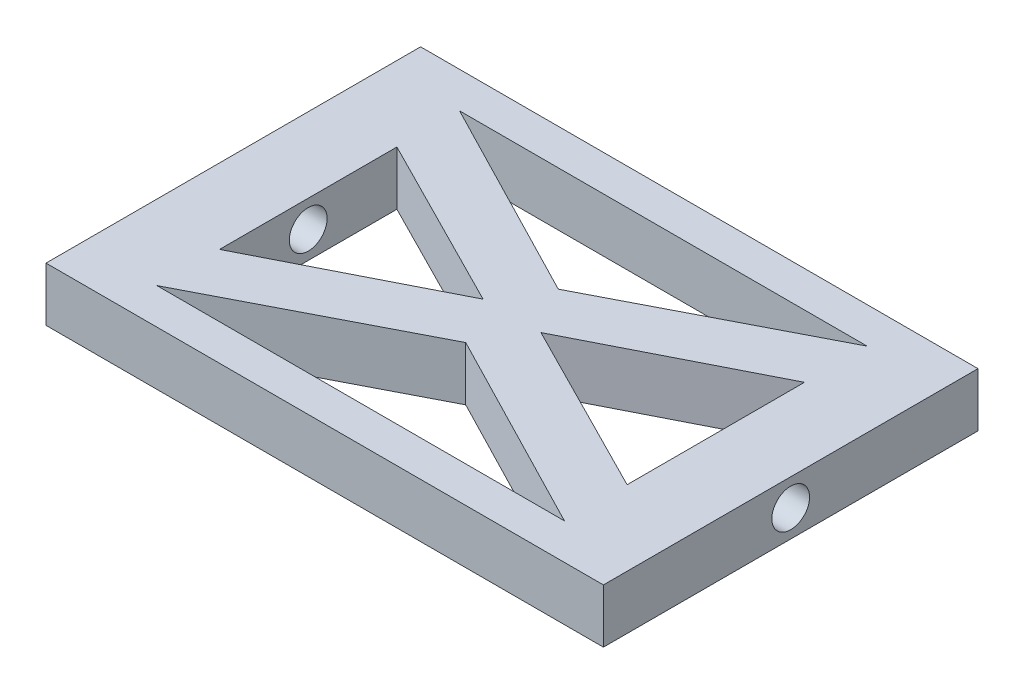
SolidWorks part; units mm, degrees
material "PLA"
ref_plane "Front" through (0, 0, 0) normal (0, 0, 1) x (1, 0, 0)
ref_plane "Top" through (0, 0, 0) normal (0, 1, 0) x (1, 0, 0)
ref_plane "Right" through (0, 0, 0) normal (1, 0, 0) x (0, 0, -1)
sketch "Sketch1" plane through (0, 0, 0) normal (0, 1, 0) x (1, 0, 0)
  line L1 (23.622, -15.875) -> (-23.622, -15.875)
  line L2 (23.622, -15.875) -> (23.622, 15.875)
  line L3 (23.622, 15.875) -> (-23.622, 15.875)
  line L4 (-23.622, -15.875) -> (-23.622, 15.875)
  line L5 (23.622, -15.875) -> (-23.622, 15.875) construction
  line L6 (23.622, 15.875) -> (-23.622, -15.875) construction
  point P0 (0, 0)
  dimension "D1" = 31.75
  dimension "D2" = 47.244
extrude "Boss-Extrude1" add sketch "Sketch1" along normal blind 4.572
sketch "Sketch2" plane through (0, 4.572, 0) normal (0, 1, 0) x (1, 0, 0)
  line L0 (-17.272, 3.175) -> (-17.272, 13.335)
  line L1 (-17.272, 13.335) -> (18.264, 13.335)
  line L2 (18.264, 13.335) -> (-17.272, 3.175)
  line L3 (23.622, 15.875) -> (-23.622, 15.875) construction
  line L4 (-23.622, 15.875) -> (-23.622, -15.875) construction
  line L5 (-17.272, -3.175) -> (-17.272, -13.335)
  line L6 (-17.272, -13.335) -> (18.264, -13.335)
  line L7 (18.264, -13.335) -> (-17.272, -3.175)
  line L8 (-23.622, -15.875) -> (23.622, -15.875) construction
  line L9 (-18.288, 13.335) -> (17.272, 13.335)
  line L10 (17.272, 13.335) -> (17.272, 3.175)
  line L11 (17.272, 3.175) -> (-18.288, 13.335)
  line L12 (23.622, -15.875) -> (23.622, 15.875) construction
  line L13 (17.272, -3.175) -> (17.272, -13.335)
  line L14 (17.272, -13.335) -> (-18.288, -13.335)
  line L15 (-18.288, -13.335) -> (17.272, -3.175)
  dimension "D1" = 10.16
  dimension "D2" = 2.54
  dimension "D3" = 6.35
  dimension "D4" = 35.536
  dimension "D5" = 35.536
  dimension "D6" = 2.54
  dimension "D7" = 10.16
  dimension "D8" = 35.56
  dimension "D9" = 6.35
  dimension "D10" = 10.16
  dimension "D11" = 35.56
  dimension "D12" = 10.16
sketch "Sketch4" plane through (23.622, 0, 0) normal (1, 0, 0) x (0, 0, -1)
  line L0 (0, 2.5146) -> (0, -2.5146) construction
  line L1 (17.4625, 0) -> (-17.4625, 0) construction
  circle A0 centre (0, 2.286) radius 1.6002
  dimension "D1" = 3.2004
  dimension "D2" = 2.286
extrude "Cut-Extrude3" cut sketch "Sketch4" against normal blind 7.62
sketch "Sketch5" plane through (-23.622, 0, 0) normal (-1, 0, 0) x (0, 0, 1)
  line L0 (0, -2.5146) -> (0, 2.5146) construction
  line L1 (17.4625, 0) -> (-17.4625, 0) construction
  circle A0 centre (0, 2.286) radius 1.6002
  dimension "D1" = 3.2004
  dimension "D2" = 2.286
extrude "Cut-Extrude4" cut sketch "Sketch5" against normal blind 7.62
sketch "Sketch6" plane through (0, 4.572, 0) normal (0, 1, 0) x (1, 0, 0)
  line L0 (0, 0) -> (-23.622, 0)
  line L1 (-23.622, 15.875) -> (-23.622, -15.875) construction
  line L2 (-23.622, 0) -> (23.622, 0)
  line L3 (23.622, -15.875) -> (23.622, 15.875) construction
  line L4 (0, 0) -> (0, 15.875)
  line L5 (23.622, 15.875) -> (-23.622, 15.875) construction
  line L6 (0, 15.875) -> (0, -15.875)
  line L7 (-23.622, -15.875) -> (23.622, -15.875) construction
  line L8 (0, 15.875) -> (0, 12.827)
  line L9 (-23.622, 12.827) -> (-17.272, 12.827)
  line L10 (-17.272, 12.827) -> (17.272, 12.827)
  line L11 (-17.272, 12.827) -> (0, 3.9214)
  line L12 (0, 3.9214) -> (0, 12.827)
  line L13 (17.272, 12.827) -> (0, 3.9214)
  line L14 (17.272, -12.827) -> (0, -3.9214)
  line L15 (-17.272, -12.827) -> (17.272, -12.827)
  line L16 (-17.272, -12.827) -> (0, -3.9214)
  line L17 (-17.272, -7.5168) -> (-17.272, 7.5168)
  line L18 (-17.272, 7.5168) -> (-2.4527, 0)
  line L19 (-2.4527, 0) -> (-9.8623, 3.7584)
  line L20 (-9.8623, 3.7584) -> (-7.7524, 7.9186)
  line L21 (-17.272, -7.5168) -> (-2.4527, 0)
  line L22 (17.272, 7.5168) -> (2.4527, 0)
  line L23 (17.272, -7.5168) -> (17.272, 7.5168)
  line L24 (17.272, -7.5168) -> (2.4527, 0)
  point P29 (-17.272, 0)
  dimension "D1" = 6.35
  dimension "D2" = 3.048
extrude "Cut-Extrude6" cut sketch "Sketch6" against normal through all contours L24 L23 L2 | L2 L23 L22 | L13 L10 L6 | L10 L11 L6 | L18 L17 L2 | L17 L21 L2 | L16 L15 L6 | L6 L15 L14 region at (12.3322, 4.572, -2.5056) region at (12.3322, 4.572, 2.5056) region at (5.7573, 4.572, 9.8585) region at (-5.7573, 4.572, 9.8585) region at (-12.3322, 4.572, 2.5056) region at (-12.3322, 4.572, -2.5056) region at (-5.7573, 4.572, -9.8585) region at (5.7573, 4.572, -9.8585)
